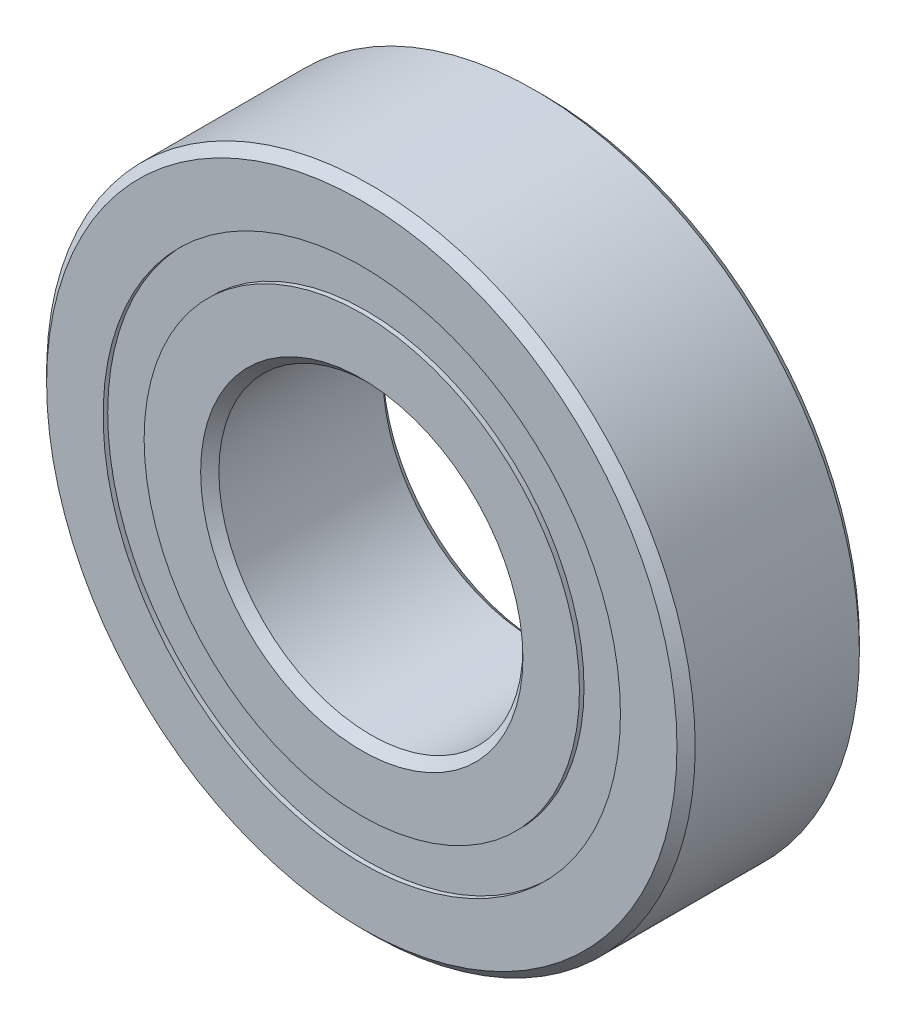
SolidWorks part; units mm, degrees
ref_plane "Front Plane" through (0, 0, 0) normal (0, 0, 1) x (1, 0, 0)
ref_plane "Top Plane" through (0, 0, 0) normal (0, 1, 0) x (1, 0, 0)
ref_plane "Right Plane" through (0, 0, 0) normal (1, 0, 0) x (0, 0, -1)
sketch "Sketch1" plane through (0, 0, 0) normal (0, 0, 1) x (1, 0, 0)
  circle A0 centre (0, 0) radius 16 construction
  circle A1 centre (0, 0) radius 7.5 construction
  dimension "OD" = 32
  dimension "Shaft Dia" = 15
sketch "Sketch2" plane through (0, 0, 0) normal (1, 0, 0) x (0, 0, -1)
  line L0 (-4.5, 0) -> (4.5, 0) construction
  line L1 (0, 16) -> (0, -16) construction
  line L2 (4.05, 16) -> (-4.05, 16) construction
  line L3 (-4.05, 16) -> (-4.5, 15.55) construction
  line L4 (-4.5, 15.55) -> (-4.5, 12.761) construction
  line L5 (-4.5, 12.761) -> (-2, 12.761) construction
  line L6 (4.5, 12.761) -> (2, 12.761) construction
  line L7 (4.5, 15.55) -> (4.5, 12.761) construction
  line L8 (4.05, 16) -> (4.5, 15.55) construction
  line L9 (0, 16) -> (0, 11.75) construction
  line L10 (0, 11.75) -> (0, 7.5) construction
  line L11 (4.5, 11.75) -> (-4.5, 11.75) construction
  line L12 (-4.5, 7.95) -> (-4.5, 10.739) construction
  line L13 (-4.05, 7.5) -> (-4.5, 7.95) construction
  line L14 (4.05, 7.5) -> (-4.05, 7.5) construction
  line L15 (4.05, 7.5) -> (4.5, 7.95) construction
  line L16 (4.5, 7.95) -> (4.5, 10.739) construction
  line L17 (4.5, 10.739) -> (2, 10.739) construction
  line L18 (-4.5, 10.739) -> (-2, 10.739) construction
  arc A0 (-2, 12.761) -> (2, 12.761) centre (0, 11.75) cw construction
  arc A1 (-2, 10.739) -> (2, 10.739) centre (0, 11.75) ccw construction
  point P14 (0, 7.5)
  point P18 (0, 11.75)
  dimension "D1" = 45
  dimension "D2" = 0.45
  dimension "D3" = 4
  dimension "D4" = 1.011
  dimension "Width" = 9
sketch "Sketch6" plane through (0, 0, 0) normal (1, 0, 0) x (0, 0, -1)
  line L0 (-4.5, 15.55) -> (-4.5, 12.761) construction
  line L1 (-4.05, 16) -> (-4.5, 15.55) construction
  line L2 (4.05, 16) -> (-4.05, 16) construction
  line L3 (4.05, 16) -> (4.5, 15.55) construction
  line L4 (4.5, 15.55) -> (4.5, 12.761) construction
  line L5 (4.5, 12.761) -> (2, 12.761) construction
  line L6 (-4.5, 12.761) -> (-2, 12.761) construction
  line L7 (-4.5, 15.55) -> (-4.5, 12.761)
  line L8 (-4.05, 16) -> (-4.5, 15.55)
  line L9 (4.05, 16) -> (-4.05, 16)
  line L10 (4.05, 16) -> (4.5, 15.55)
  line L11 (4.5, 15.55) -> (4.5, 12.761)
  line L12 (4.5, 12.761) -> (2, 12.761)
  line L13 (-4.5, 12.761) -> (-2, 12.761)
  line L14 (-4.5, 7.95) -> (-4.5, 10.739) construction
  line L15 (-4.05, 7.5) -> (-4.5, 7.95) construction
  line L16 (4.05, 7.5) -> (-4.05, 7.5) construction
  line L17 (4.05, 7.5) -> (4.5, 7.95) construction
  line L18 (4.5, 7.95) -> (4.5, 10.739) construction
  line L19 (4.5, 10.739) -> (2, 10.739) construction
  line L20 (-4.5, 10.739) -> (-2, 10.739) construction
  line L21 (-4.5, 7.95) -> (-4.5, 10.739)
  line L22 (-4.05, 7.5) -> (-4.5, 7.95)
  line L23 (4.05, 7.5) -> (-4.05, 7.5)
  line L24 (4.05, 7.5) -> (4.5, 7.95)
  line L25 (4.5, 7.95) -> (4.5, 10.739)
  line L26 (4.5, 10.739) -> (2, 10.739)
  line L27 (-4.5, 10.739) -> (-2, 10.739)
  arc A0 (2, 12.761) -> (-2, 12.761) centre (0, 11.75) ccw construction
  arc A1 (2, 12.761) -> (-2, 12.761) centre (0, 11.75) ccw
  arc A2 (-2, 10.739) -> (2, 10.739) centre (0, 11.75) ccw construction
  arc A3 (-2, 10.739) -> (2, 10.739) centre (0, 11.75) ccw
revolve "Revolve1" add sketch "Sketch6" angle 360 about L0
sketch "Sketch4" plane through (0, 0, 0) normal (1, 0, 0) x (0, 0, -1)
  line L0 (-2.241, 11.75) -> (2.241, 11.75)
  arc A2 (-2.241, 11.75) -> (2.241, 11.75) centre (0, 11.75) cw
  arc A3 (2, 12.761) -> (-2, 12.761) centre (0, 11.75) ccw construction
revolve "Revolve2" add sketch "Sketch4" angle 360 about L0
ref_axis "Axis1" through (0, 0, -4.5) along (0, 0, 1)
pattern_circular "CirPattern1" count 12 every 30 about axis through (0, 0, -4.5) along (0, 0, 1) of bodies 104
sketch "Sketch5" plane through (0, 0, 0) normal (1, 0, 0) x (0, 0, -1)
  line L0 (-4.5, 12.761) -> (-2, 12.761) construction
  line L1 (-4.275, 12.761) -> (-2.241, 12.761)
  line L2 (-4.275, 12.761) -> (-4.275, 10.739)
  line L3 (-4.275, 10.739) -> (-2.241, 10.739)
  line L4 (-2.241, 12.761) -> (-2.241, 10.739)
  line L6 (4.5, 12.761) -> (2, 12.761) construction
  line L7 (4.275, 12.761) -> (2.241, 12.761)
  line L8 (4.275, 12.761) -> (4.275, 10.739)
  line L9 (4.275, 10.739) -> (2.241, 10.739)
  line L10 (2.241, 12.761) -> (2.241, 10.739)
  line L12 (-4.05, 16) -> (-4.5, 15.55) construction
  line L13 (-4.5, 10.739) -> (-2, 10.739) construction
  line L14 (4.5, 10.739) -> (2, 10.739) construction
  point P18 (-4.275, 15.775)
revolve "Revolve3" add sketch "Sketch5" angle 360 about L0
equation "\"D2@Sketch2\"= \"Width@Sketch2\" * .05"
equation "\"D3@Sketch2\"=\"Width@Sketch2\" / 2.25"
equation "\"D4@Sketch2\"= ( ( ( \"OD@Sketch1\" - \"Width@Sketch2\" ) / 2 ) / 3.25 ) / 3.5"
equation "\"D2@CirPattern1\" = 360/\"Balls@CirPattern1\""
